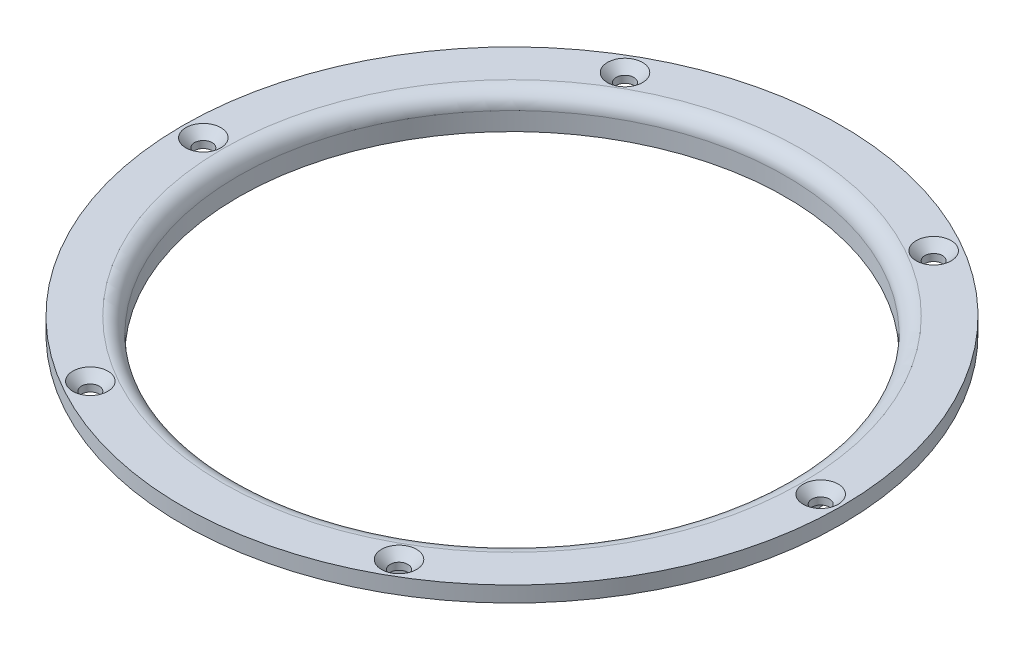
SolidWorks part; units mm, degrees
material "PET"
ref_plane "Front Plane" through (0, 0, 0) normal (0, 0, 1) x (1, 0, 0)
ref_plane "Top Plane" through (0, 0, 0) normal (0, 1, 0) x (1, 0, 0)
ref_plane "Right Plane" through (0, 0, 0) normal (1, 0, 0) x (0, 0, -1)
sketch "Sketch2" plane through (0, 0, 0) normal (0, 0, 1) x (1, 0, 0)
  line L0 (-55, 8.3) -> (-52.5, 8.3)
  line L1 (-52.5, 8.3) -> (-52.5, 14.8)
  line L2 (-52.5, 14.8) -> (-63.2, 14.8)
  line L3 (-63.2, 14.8) -> (-63.2, 11.8)
  line L4 (-63.2, 11.8) -> (-55, 11.8)
  line L5 (-55, 11.8) -> (-55, 8.3)
  line L11 (0, 0) -> (0, 30.013) construction
sketch "Sketch3" plane through (0, 0, 0) normal (0, 0, 1) x (1, 0, 0)
  line L6 (-55, 8.3) -> (-52.5, 8.3)
  line L7 (-52.5, 8.3) -> (-52.5, 14.8)
  line L8 (-52.5, 14.8) -> (-63.2, 14.8)
  line L9 (-63.2, 14.8) -> (-63.2, 11.8)
  line L10 (-63.2, 11.8) -> (-55, 11.8)
  line L11 (-55, 11.8) -> (-55, 8.3)
  line L12 (-55, 8.3) -> (-52.5, 8.3)
  line L13 (-52.5, 8.3) -> (-52.5, 14.8)
  line L14 (-52.5, 14.8) -> (-63.2, 14.8)
  line L15 (-63.2, 14.8) -> (-63.2, 11.8)
  line L16 (-63.2, 11.8) -> (-55, 11.8)
  line L17 (-55, 11.8) -> (-55, 8.3)
  dimension "D1" = 0
revolve "Cap" add sketch "Sketch3" angle 360 about L11
sketch "Sketch9" plane through (0, 0, 0) normal (0, 0, 1) x (1, 0, 0)
  line L0 (-63.2, 11.8) -> (-55.2, 11.8) construction
  line L4 (-59.2, 11.8) -> (-59.2, 4.8)
  line L5 (-59.2, 11.8) -> (-57.7, 11.8)
  line L6 (-59.2, 11.8) -> (-57.5, 11.8)
  point P3 (-59.2, 11.8)
sketch "Sketch10" plane through (0, 0, 0) normal (0, 1, 0) x (1, 0, 0)
  circle A0 centre (-59.2, 0) radius 1.7
  point P0 (-59.2, 0)
  point P1 (-57.5, 0)
hole_wizard "CSK for M3 SFHCS1" positions "Sketch11" profile "Sketch12" countersink size "M3" standard "ANSI Metric"
sketch "Sketch11" plane through (0, 14.8, 0) normal (0, 1, 0) x (1, 0, 0)
  point P0 (-59.2, 0)
sketch "Sketch12" plane through (-59.2, 14.8, 0) normal (1, 0, 0) x (0, 0, 1)
  line L0 (0, 0) -> (0, 9.9115)
  line L1 (0, 9.9115) -> (1.7, 8.89)
  line L2 (1.7, 8.89) -> (1.7, 1.66)
  line L3 (1.7, 1.66) -> (3.36, 0)
  line L5 (3.36, 0) -> (0, 0)
  line L6 (-1.7, 1.66) -> (-3.36, 0) construction
  line L10 (0, 9.9115) -> (-1.7, 8.89) construction
  line L11 (0, -6.35) -> (0, 107.95) construction
  dimension "Hole Dia." = 3.4
  dimension "Hole Depth" = 8.89
  dimension "Near C'Sink Dia." = 6.72
  dimension "Near C'Sink Angle" = 90
  dimension "Drill Angle" = 118
pattern_circular "CirPattern1" count 6 over 360 about axis through (0, 0, 0) along (0, 1, 0) of "CSK for M3 SFHCS1" reverse direction yes
fillet "Fillet1" radius 3 1 edges at (52.5, 14.8, 0)
equation "\"TopHoles\"= 6"
equation "\"D1@CirPattern1\"=\"TopHoles\""
